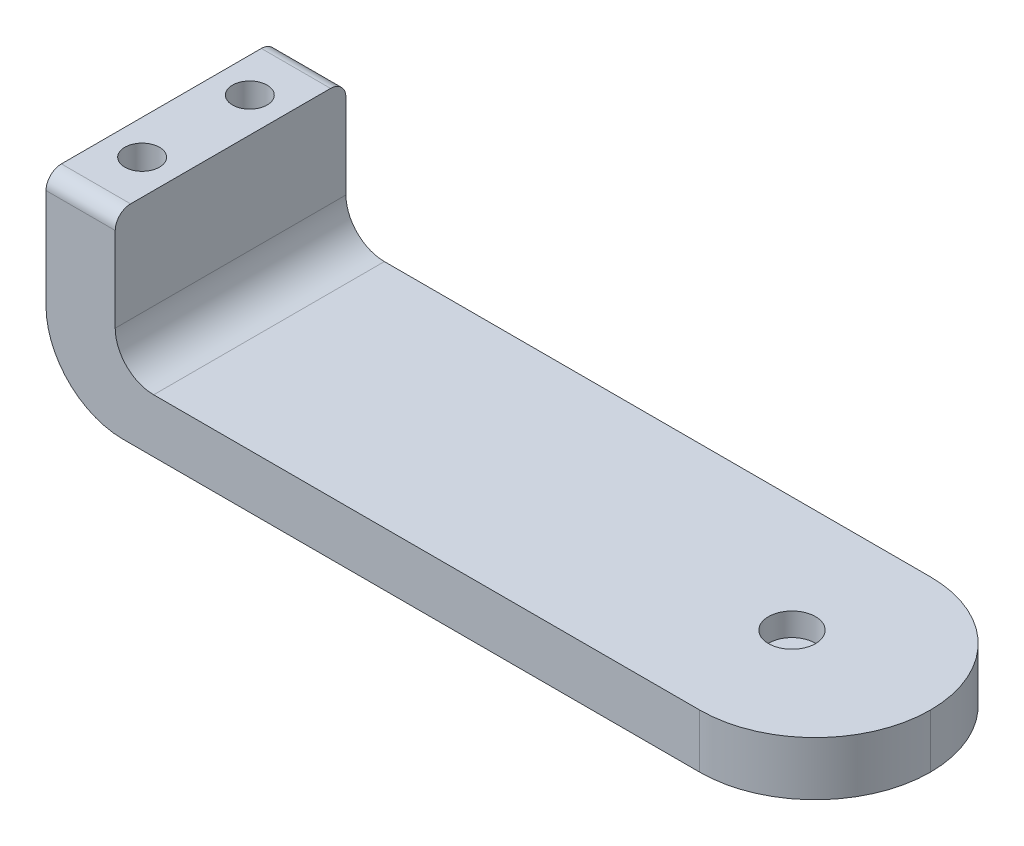
SolidWorks part; units mm, degrees
ref_plane "Front Plane" through (0, 0, 0) normal (0, 0, 1) x (1, 0, 0)
ref_plane "Top Plane" through (0, 0, 0) normal (0, 1, 0) x (1, 0, 0)
ref_plane "Right Plane" through (0, 0, 0) normal (1, 0, 0) x (0, 0, -1)
sketch "Sketch1" plane through (0, 0, 0) normal (0, 0, 1) x (1, 0, 0)
  line L0 (0, 0) -> (0, 21.5) construction
  line L1 (0, 0) -> (77, 0) construction
  line L2 (-4.5, 21.5) -> (4.5, 21.5)
  line L3 (-4.5, 21.5) -> (-4.5, -3.5)
  line L4 (-4.5, -3.5) -> (95.5, -3.5)
  line L5 (95.5, -3.5) -> (95.5, 3.5)
  line L6 (95.5, 3.5) -> (4.5, 3.5)
  line L7 (4.5, 3.5) -> (4.5, 21.5)
  line L8 (77, 0) -> (95.5, 0) construction
  point P6 (0, 21.5)
  dimension "D1" = 77
  dimension "D2" = 9
  dimension "D3" = 7
  dimension "D4" = 18
  dimension "D5" = 100
extrude "Boss-Extrude1" add sketch "Sketch1" along normal blind 30
sketch "Sketch2" plane through (0, 21.5, 0) normal (0, 1, 0) x (1, 0, 0)
  line L0 (0, -30) -> (0, 0) construction
  line L1 (4.5, -30) -> (-4.5, -30) construction
  line L2 (4.5, -15) -> (-4.5, -15) construction
  line L3 (4.5, -30) -> (4.5, 0) construction
  line L4 (-4.5, -30) -> (-4.5, 0) construction
  circle A0 centre (0, -22) radius 2.25
  circle A1 centre (0, -8) radius 2.25
  dimension "D1" = 4.5
  dimension "D2" = 4.5
  dimension "D3" = 14
  dimension "D4" = 7
extrude "Cut-Extrude1" cut sketch "Sketch2" against normal blind 6
fillet "Fillet1" radius 5 1 edges at (4.5, 3.5, 15)
fillet "Fillet2" radius 10 1 edges at (-4.5, -3.5, 15)
sketch "Sketch3" plane through (0, 3.5, 0) normal (0, -1, 0) x (1, 0, 0)
  line L0 (-4.5, 15) -> (77.5, 15) construction
  line L1 (-4.5, 0) -> (-4.5, 30) construction
  circle A0 centre (77.5, 15) radius 3.05
  dimension "D1" = 6.1
  dimension "D2" = 82
extrude "Cut-Extrude3" cut sketch "Sketch3" along normal blind 3 contours A0
fillet "Fillet3" radius 15 2 edges at (95.5, 0, 30) (95.5, 0, 0)
fillet "Fillet4" radius 2 2 edges at (0, 21.5, 0) (0, 21.5, 30)
